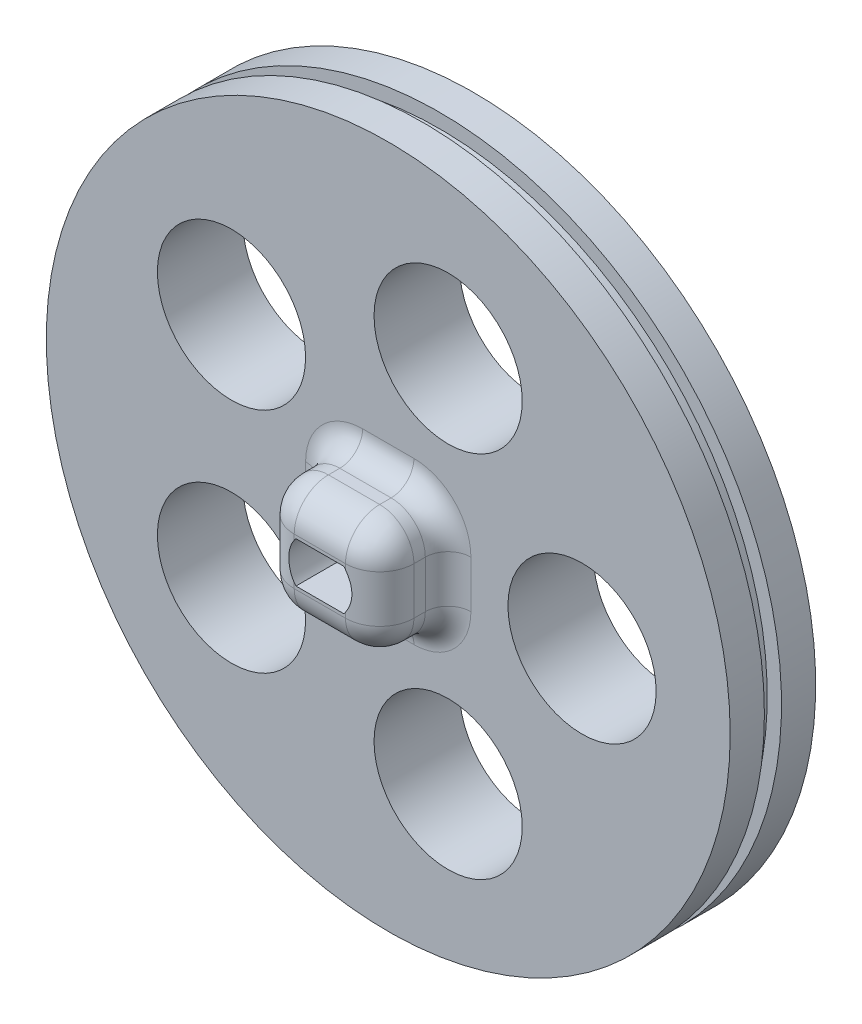
SolidWorks part; units mm, degrees
ref_plane "Plan de face" through (0, 0, 0) normal (0, 0, 1) x (1, 0, 0)
ref_plane "Plan de dessus" through (0, 0, 0) normal (0, 1, 0) x (1, 0, 0)
ref_plane "Plan de droite" through (0, 0, 0) normal (1, 0, 0) x (0, 0, -1)
sketch "Esquisse2" plane through (0, 0, 0) normal (0, 0, 1) x (1, 0, 0)
  line L0 (0, 0) -> (39.5063, 0) construction
  circle A0 centre (0, 0) radius 30
  dimension "D1" = 60
extrude "Boss.-Extru.1" add sketch "Esquisse2" along normal blind 3
sketch "Esquisse4" plane through (0, 0, 3) normal (0, 0, 1) x (1, 0, 0)
  line L1 (-2.1, -1.8) -> (2.1, -1.8)
  line L2 (-2.1, -1.8) -> (-2.1, 1.8) construction
  line L3 (-2.1, 1.8) -> (2.1, 1.8)
  line L4 (2.1, -1.8) -> (2.1, 1.8) construction
  line L5 (-2.1, -1.8) -> (2.1, 1.8) construction
  line L6 (-2.1, 1.8) -> (2.1, -1.8) construction
  arc A0 (-2.1, -1.8) -> (-2.1, 1.8) centre (0, 0) cw
  arc A1 (2.1, 1.8) -> (2.1, -1.8) centre (0, 0) cw
  point P0 (0, 0)
  dimension "D1" = 4.2
  dimension "D2" = 3.6
extrude "Enlèv. mat.-Extru.1" cut sketch "Esquisse4" against normal through all
sketch "Esquisse5" plane through (0, 0, 3) normal (0, 0, 1) x (1, 0, 0)
  line L0 (-2.1, 1.8) -> (2.1, 1.8)
  line L1 (5.2507, -5.0723) -> (-5.2507, -5.0723)
  line L2 (5.2507, -5.0723) -> (5.2507, 5.0723)
  line L3 (5.2507, 5.0723) -> (-5.2507, 5.0723)
  line L4 (-5.2507, -5.0723) -> (-5.2507, 5.0723)
  line L5 (5.2507, -5.0723) -> (-5.2507, 5.0723) construction
  line L6 (5.2507, 5.0723) -> (-5.2507, -5.0723) construction
  line L7 (-2.1, -1.8) -> (2.1, -1.8) construction
  line L8 (-2.1, -1.8) -> (2.1, -1.8)
  arc A0 (-2.1, -1.8) -> (-2.1, 1.8) centre (0, 0) cw
  arc A1 (2.1, 1.8) -> (2.1, -1.8) centre (0, 0) cw
  point P0 (0, 0)
  arc M1 (2.1, 1.8) -> (2.1, -1.8) centre (0, 0) cw
  line M2 (2.1, -1.8) -> (-2.1, -1.8)
  arc M3 (-2.1, -1.8) -> (-2.1, 1.8) centre (0, 0) cw
  line M4 (-2.1, 1.8) -> (2.1, 1.8)
extrude "Boss.-Extru.3" add sketch "Esquisse5" along normal blind 6 contours L4 L1 L2 L3 M4 M1 M2 M3 region at (0, -4.9263, 3)
sketch "Esquisse8" plane through (0, 0, 0) normal (0, 0, -1) x (-1, 0, 0)
  circle A0 centre (0, 0) radius 28.75
  dimension "D1" = 57.5
extrude "Boss.-Extru.4" add sketch "Esquisse8" along normal blind 1.5
sketch "Esquisse9" plane through (0, 0, -1.5) normal (0, 0, -1) x (-1, 0, 0)
  circle A0 centre (0, 0) radius 30
  dimension "D1" = 60
extrude "Boss.-Extru.5" add sketch "Esquisse9" along normal blind 3
sketch "Esquisse10" plane through (0, 0, 0) normal (0, 0, 1) x (1, 0, 0)
  line L0 (-2.1, 1.8) -> (2.1, 1.8)
  line L2 (2.1, -1.8) -> (-2.1, -1.8)
  line L3 (2.1, -1.8) -> (-2.1, -1.8) construction
  line L4 (-2.1, -1.8) -> (2.1, -1.8) construction
  arc A0 (-2.1, 1.8) -> (-2.1, -1.8) centre (0, 0) ccw
  arc A1 (-2.1, 1.8) -> (-2.1, -1.8) centre (0, 0) ccw construction
  arc A2 (2.1, 1.8) -> (2.1, -1.8) centre (0, 0) cw
  arc A3 (2.1, -1.8) -> (2.1, 1.8) centre (0, 0) ccw construction
  dimension "D2" = 2.7659
  dimension "D3" = 4.2
  dimension "D1" = 3.6
extrude "Enlèv. mat.-Extru.4" cut sketch "Esquisse10" against normal through all
fillet "Congé1" radius 3 8 edges at (-5.2507, 5.0723, 6) (-5.2507, -5.0723, 6) (-5.2507, 0, 9) (0, -5.0723, 9) (5.2507, -5.0723, 6) (5.2507, 0, 9) (5.2507, 5.0723, 6) (0, 5.0723, 9)
fillet "Congé2" radius 2 8 edges at (4.372, 4.1936, 3) (5.2507, 0, 3) (4.372, -4.1936, 3) (0, -5.0723, 3) (-4.372, -4.1936, 3) (-5.2507, 0, 3) (-4.372, 4.1936, 3) (0, 5.0723, 3)
sketch "Esquisse11" plane through (0, 0, -4.5) normal (0, 0, -1) x (-1, 0, 0)
  circle A0 centre (-17, 0) radius 6.5
  circle A1 centre (-5.2533, 16.168) radius 6.5
  circle A2 centre (13.7533, 9.9923) radius 6.5
  circle A3 centre (13.7533, -9.9923) radius 6.5
  circle A4 centre (-5.2533, -16.168) radius 6.5
extrude "Ajourage" cut sketch "Esquisse11" against normal through all
